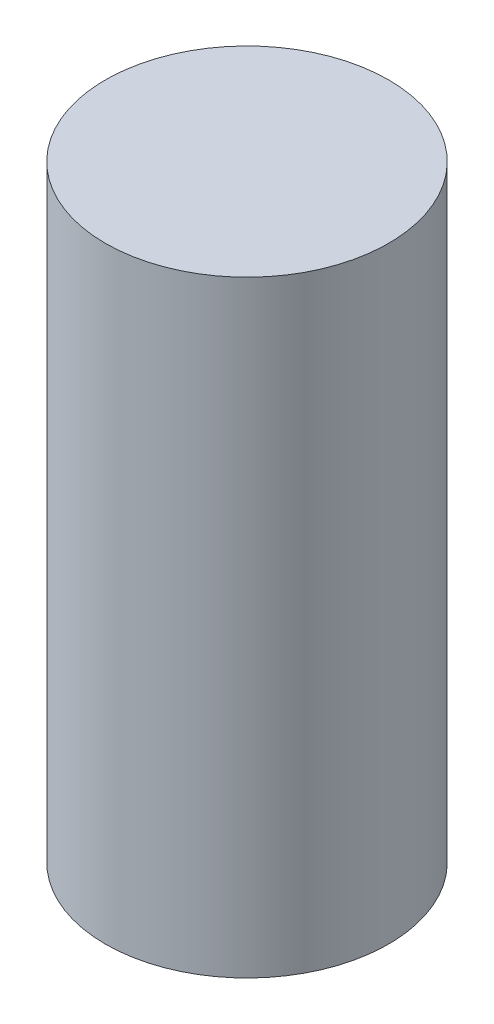
SolidWorks part; units mm, degrees
ref_plane "Front Plane" through (0, 0, 0) normal (0, 0, 1) x (1, 0, 0)
ref_plane "Top Plane" through (0, 0, 0) normal (0, 1, 0) x (1, 0, 0)
ref_plane "Right Plane" through (0, 0, 0) normal (1, 0, 0) x (0, 0, -1)
sketch "Sketch1" plane through (0, 0, 0) normal (0, 1, 0) x (1, 0, 0)
  circle A0 centre (0, 0) radius 35
  dimension "D1" = 70
extrude "Boss-Extrude1" add sketch "Sketch1" along normal blind 150
